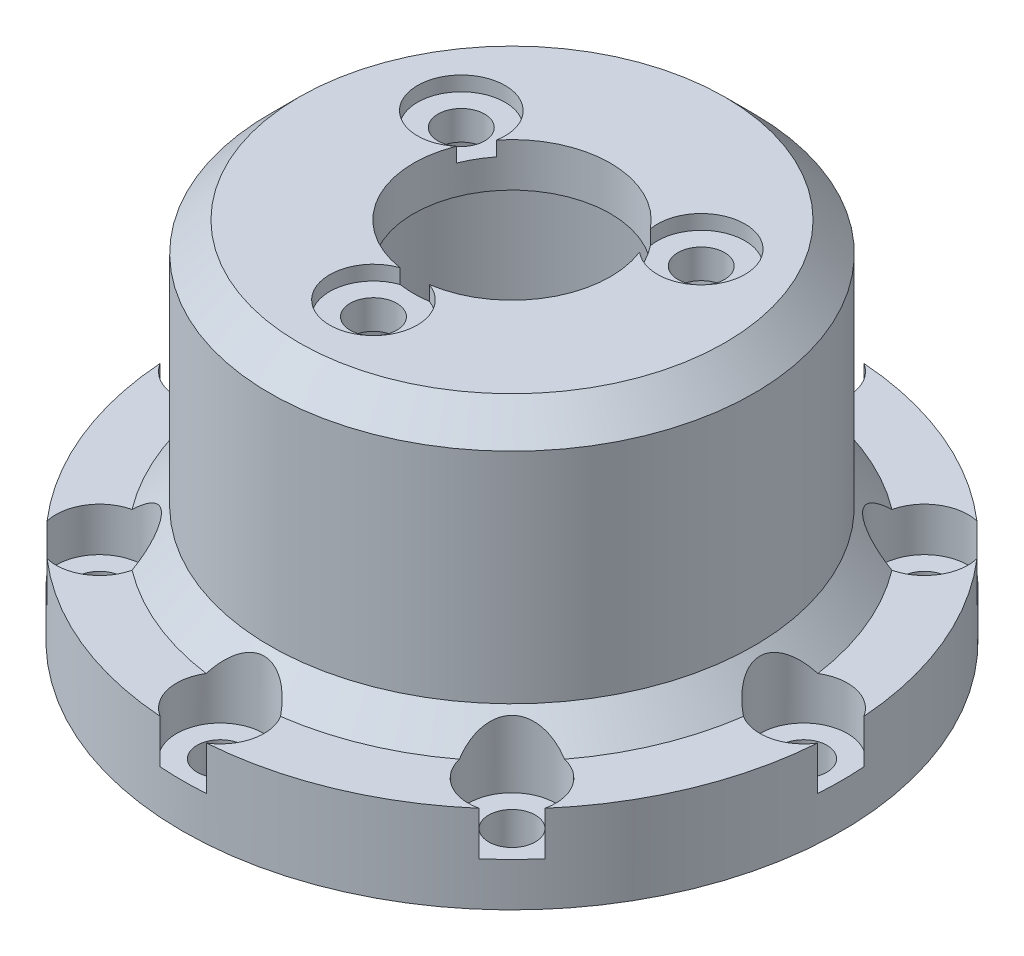
SolidWorks part; units mm, degrees
other "细节项目1"
material "6061-T6 (SS)"
ref_plane "前视基准面" through (0, 0, 0) normal (0, 0, 1) x (1, 0, 0)
ref_plane "上视基准面" through (0, 0, 0) normal (0, 1, 0) x (1, 0, 0)
ref_plane "右视基准面" through (0, 0, 0) normal (1, 0, 0) x (0, 0, -1)
sketch "草图1" plane through (0, 0, 0) normal (0, 0, 1) x (1, 0, 0)
  line L0 (0, 0) -> (0, 36.8725) construction
  line L1 (-14, 0) -> (-16.6, 0)
  line L2 (-16.6, 0) -> (-16.6, 3)
  line L3 (-16.6, 3) -> (-22.6, 3)
  line L4 (-22.6, 3) -> (-22.6, 9)
  line L5 (-22.6, 9) -> (-16.6, 9)
  line L6 (-16.6, 9) -> (-16.6, 28)
  line L7 (-16.6, 28) -> (-6.75, 28)
  line L8 (-6.75, 28) -> (-6.75, 25)
  line L9 (-6.75, 25) -> (-14, 25)
  line L10 (-14, 25) -> (-14, 0)
  dimension "D1" = 28
  dimension "D2" = 33.2
  dimension "D3" = 2.6
  dimension "D4" = 3
  dimension "D5" = 6
  dimension "D6" = 6
  dimension "D8" = 3
  dimension "D9" = 25
  dimension "D10" = 13.5
revolve "旋转1" add sketch "草图1" angle 360 about L0
sketch "草图2" plane through (0, 3, 0) normal (0, -1, 0) x (1, 0, 0)
  circle A0 centre (0, 0) radius 20 construction
  circle A1 centre (0, -20) radius 1.6
  dimension "D1" = 40
  dimension "D2" = 3.2
extrude "切除-拉伸1" cut sketch "草图2" against normal blind 8
pattern_circular "阵列(圆周)1" count 8 over 360 about axis through (0, 3, 0) along (0, -1, 0) of "切除-拉伸1"
sketch "草图3" plane through (0, 28, 0) normal (0, 1, 0) x (1, 0, 0)
  circle A0 centre (0, 0) radius 9.5 construction
  circle A1 centre (0, -9.5) radius 1.6
  circle A2 centre (-8.2272, 4.75) radius 1.6
  circle A3 centre (8.2272, 4.75) radius 1.6
  point P11 (0, 0)
  dimension "D1" = 19
  dimension "D2" = 3.2
  dimension "D3" = 3
extrude "切除-拉伸2" cut sketch "草图3" against normal blind 10
sketch "草图4" plane through (0, 9, 0) normal (0, 1, 0) x (1, 0, 0)
  circle A0 centre (20, 0) radius 3
  dimension "D1" = 6
extrude "切除-拉伸6" cut sketch "草图4" against normal blind 3 contours A0
pattern_circular "阵列(圆周)2" count 8 over 360 about axis through (0, 9, 0) along (0, -1, 0) of "切除-拉伸6"
sketch "草图5" plane through (0, 28, 0) normal (0, 1, 0) x (1, 0, 0)
  circle A0 centre (8.2272, 4.75) radius 3
  dimension "D1" = 6
extrude "切除-拉伸7" cut sketch "草图5" against normal blind 1
pattern_circular "阵列(圆周)3" count 3 over 360 about axis through (0, 28, 0) along (0, -1, 0) of "切除-拉伸7"
chamfer "倒角1" distance 2 angle 45 2 edges at (0, 9, -16.6) (0, 28, -16.6)
